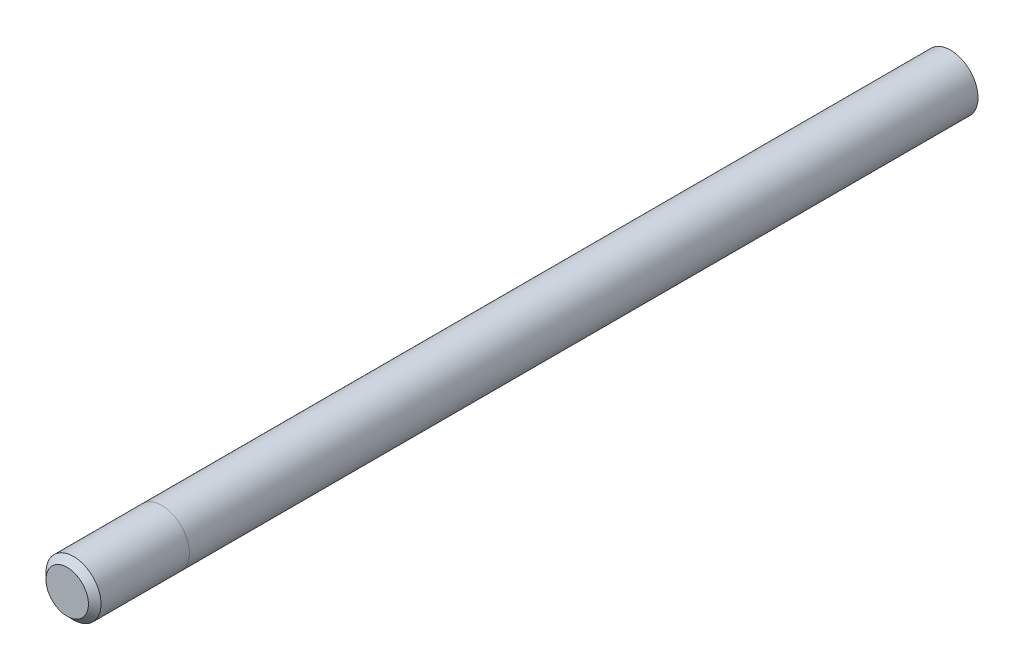
SolidWorks part; units mm, degrees
ref_plane "Front" through (0, 0, 0) normal (0, 0, 1) x (1, 0, 0)
ref_plane "Top" through (0, 0, 0) normal (0, 1, 0) x (1, 0, 0)
ref_plane "Right" through (0, 0, 0) normal (1, 0, 0) x (0, 0, -1)
sketch "Sketch1" plane through (0, 0, 0) normal (0, 0, 1) x (1, 0, 0)
  circle A0 centre (0, 0) radius 5.5372
  dimension "D1" = 11.0744
extrude "Boss-Extrude1" add sketch "Sketch1" along normal blind 158.75
sketch "Sketch2" plane through (0, 0, 158.75) normal (0, 0, 1) x (1, 0, 0)
  circle A0 centre (0, 0) radius 5.5372 construction
  circle A1 centre (0, 0) radius 5.5372
extrude "Boss-Extrude2" add sketch "Sketch2" along normal blind 19.05 separate body
chamfer "Chamfer1" distance 1.27 angle 45 1 edges at (5.5372, 0, 177.8)
